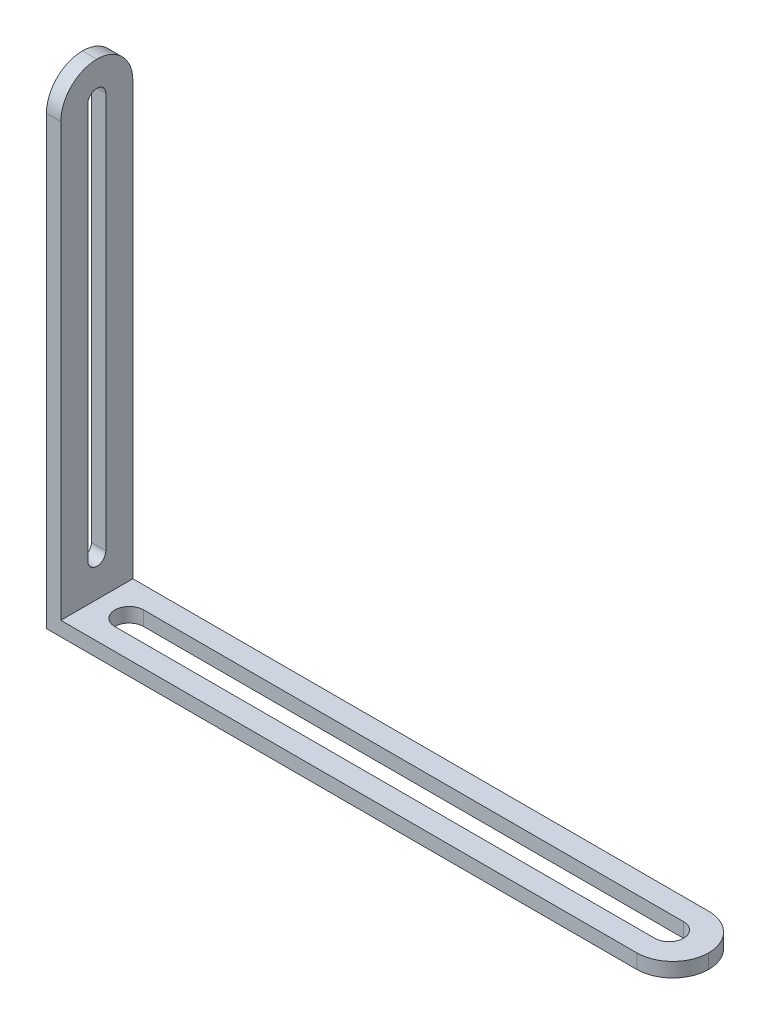
SolidWorks part; units mm, degrees
material "1060 Alloy"
ref_plane "Front Plane" through (0, 0, 0) normal (0, 0, 1) x (1, 0, 0)
ref_plane "Top Plane" through (0, 0, 0) normal (0, 1, 0) x (1, 0, 0)
ref_plane "Right Plane" through (0, 0, 0) normal (1, 0, 0) x (0, 0, -1)
sketch "Sketch1" plane through (0, 0, 0) normal (0, 0, 1) x (1, 0, 0)
  line L0 (0, 170.18) -> (5.08, 170.18)
  line L1 (5.08, 170.18) -> (5.08, 5.08)
  line L2 (5.08, 5.08) -> (220.98, 5.08)
  line L3 (220.98, 5.08) -> (220.98, 0)
  line L4 (220.98, 0) -> (0, 0)
  line L5 (0, 0) -> (0, 170.18)
  dimension "D1" = 215.9
  dimension "D2" = 165.1
  dimension "D3" = 170.18
  dimension "D4" = 5.08
extrude "Boss-Extrude1" add sketch "Sketch1" against normal blind 25.4
fillet "Fillet1" radius 12.7 4 edges at (220.98, 2.54, -25.4) (220.98, 2.54, 0) (2.54, 170.18, -25.4) (2.54, 170.18, 0)
sketch "Sketch4" plane through (5.08, 0, 0) normal (1, 0, 0) x (0, 0, -1)
  line L0 (-5.3539, 158.115) -> (45.0323, 158.115) construction
  line L1 (12.7, 170.18) -> (12.7, 5.08) construction
  line L2 (25.4, 5.08) -> (0, 5.08) construction
  line L3 (9.525, 158.115) -> (9.525, 18.415)
  line L4 (15.875, 158.115) -> (15.875, 18.415)
  line L5 (9.525, 18.415) -> (15.875, 18.415) construction
  arc A0 (15.875, 158.115) -> (9.525, 158.115) centre (12.7, 158.115) ccw
  arc A1 (9.525, 18.415) -> (15.875, 18.415) centre (12.7, 18.415) ccw
  dimension "D2" = 139.7
  dimension "D1" = 12.065
  dimension "D3" = 139.7
extrude "Cut-Extrude1" cut sketch "Sketch4" against normal blind 25.4
sketch "Sketch5" plane through (0, 5.08, 0) normal (0, 1, 0) x (1, 0, 0)
  line L0 (220.98, 39.5553) -> (220.98, -13.2942) construction
  line L1 (207.01, 38.6942) -> (207.01, -13.2942) construction
  line L2 (220.98, 12.7) -> (5.08, 12.7) construction
  line L3 (5.08, 25.4) -> (5.08, 0) construction
  line L4 (207.01, 17.78) -> (16.51, 17.78)
  line L5 (207.01, 7.62) -> (16.51, 7.62)
  arc A0 (207.01, 7.62) -> (207.01, 17.78) centre (207.01, 12.7) ccw
  arc A1 (16.51, 17.78) -> (16.51, 7.62) centre (16.51, 12.7) ccw
  point P9 (207.01, 12.7)
  dimension "D2" = 190.5
  dimension "D1" = 13.97
extrude "Cut-Extrude3" cut sketch "Sketch5" against normal blind 25.4
